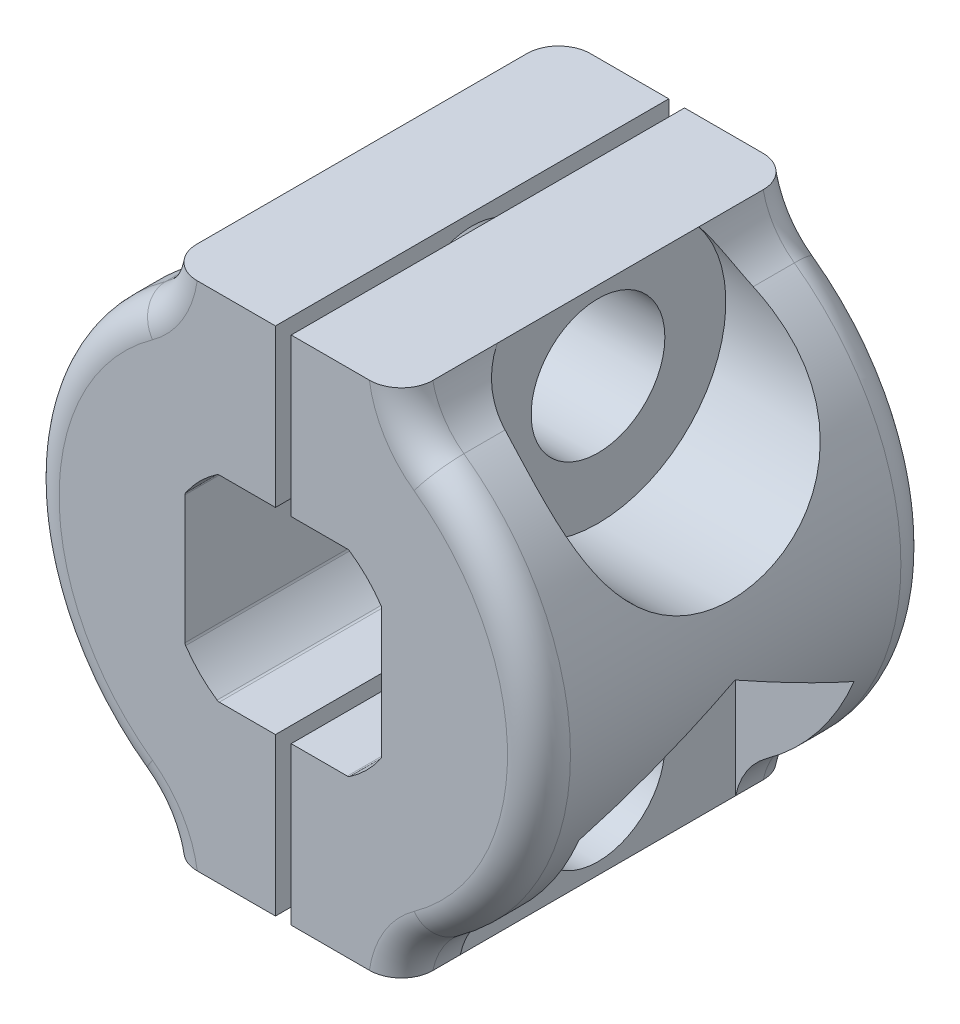
SolidWorks part; units mm, degrees
ref_plane "Front Plane" through (0, 0, 0) normal (0, 0, 1) x (1, 0, 0)
ref_plane "Top Plane" through (0, 0, 0) normal (0, 1, 0) x (1, 0, 0)
ref_plane "Right Plane" through (0, 0, 0) normal (1, 0, 0) x (0, 0, -1)
sketch "Sketch1" plane through (0, 0, 0) normal (0, 0, 1) x (1, 0, 0)
  line L6 (-3.175, 0) -> (-3.175, -2.0674)
  line L7 (-2.0674, -3.175) -> (2.0674, -3.175)
  line L8 (3.175, -2.0674) -> (3.175, 0)
  line L9 (-3.175, 2.0674) -> (-3.175, 0)
  line L10 (3.175, 0) -> (3.175, 2.0674)
  line L11 (2.0674, 3.175) -> (-2.0674, 3.175)
  arc A14 (-3.175, -2.0674) -> (-3.1531, -2.1387) centre (-3.048, -2.0674) ccw
  arc A15 (-3.1531, -2.1387) -> (-2.1387, -3.1531) centre (0, 0) ccw
  arc A16 (-2.1387, -3.1531) -> (-2.0674, -3.175) centre (-2.0674, -3.048) ccw
  arc A17 (2.0674, -3.175) -> (2.1387, -3.1531) centre (2.0674, -3.048) ccw
  arc A18 (2.1387, -3.1531) -> (3.1531, -2.1387) centre (0, 0) ccw
  arc A19 (3.1531, -2.1387) -> (3.175, -2.0674) centre (3.048, -2.0674) ccw
  arc A20 (-3, 0) -> (3, 0) centre (0, 0) ccw
  arc A21 (3, 0) -> (-3, 0) centre (0, 0) ccw
  arc A22 (3.175, 2.0674) -> (3.1531, 2.1387) centre (3.048, 2.0674) ccw
  arc A23 (3.1531, 2.1387) -> (2.1387, 3.1531) centre (0, 0) ccw
  arc A24 (2.1387, 3.1531) -> (2.0674, 3.175) centre (2.0674, 3.048) ccw
  arc A25 (-2.0674, 3.175) -> (-2.1387, 3.1531) centre (-2.0674, 3.048) ccw
  arc A26 (-2.1387, 3.1531) -> (-3.1531, 2.1387) centre (0, 0) ccw
  arc A27 (-3.1531, 2.1387) -> (-3.175, 2.0674) centre (-3.048, 2.0674) ccw
sketch "Sketch2" plane through (0, 0, 0) normal (0, 0, 1) x (1, 0, 0)
  line L0 (0, 8.255) -> (0, -8.255) construction
  line L1 (0.254, 8.2511) -> (0.254, -8.2511)
  line L2 (-0.254, 8.2511) -> (-0.254, -8.2511)
  line L3 (-0.254, 8.2511) -> (-3.81, 8.2511)
  line L4 (-3.81, 8.2511) -> (-3.81, 7.3232)
  line L5 (3.81, 8.2511) -> (3.81, 7.3232)
  line L6 (0.254, 8.2511) -> (3.81, 8.2511)
  line L7 (-3.175, 2.0674) -> (-3.175, 0)
  line L8 (-3.175, 0) -> (-3.175, -2.0674)
  line L9 (-2.0674, -3.175) -> (2.0674, -3.175)
  line L10 (3.175, -2.0674) -> (3.175, 0)
  line L11 (3.175, 0) -> (3.175, 2.0674)
  line L12 (2.0674, 3.175) -> (-2.0674, 3.175)
  line L13 (-3.175, 2.0674) -> (-3.175, 0)
  line L14 (-3.175, 0) -> (-3.175, -2.0674)
  line L15 (-2.0674, -3.175) -> (2.0674, -3.175)
  line L16 (3.175, -2.0674) -> (3.175, 0)
  line L17 (3.175, 0) -> (3.175, 2.0674)
  line L18 (2.0674, 3.175) -> (-2.0674, 3.175)
  line L19 (0, 0) -> (-8.255, 0) construction
  line L20 (-3.81, -8.2511) -> (-3.81, -7.3232)
  line L21 (-0.254, -8.2511) -> (-3.81, -8.2511)
  line L22 (3.81, -8.2511) -> (3.81, -7.3232)
  line L23 (0.254, -8.2511) -> (3.81, -8.2511)
  circle A0 centre (0, 0) radius 8.255
  arc A17 (-3.1531, 2.1387) -> (-3.175, 2.0674) centre (-3.048, 2.0674) ccw
  arc A18 (-3.175, -2.0674) -> (-3.1531, -2.1387) centre (-3.048, -2.0674) ccw
  arc A19 (-3.1531, -2.1387) -> (-2.1387, -3.1531) centre (0, 0) ccw
  arc A20 (-2.1387, -3.1531) -> (-2.0674, -3.175) centre (-2.0674, -3.048) ccw
  arc A21 (2.0674, -3.175) -> (2.1387, -3.1531) centre (2.0674, -3.048) ccw
  arc A22 (2.1387, -3.1531) -> (3.1531, -2.1387) centre (0, 0) ccw
  arc A23 (3.1531, -2.1387) -> (3.175, -2.0674) centre (3.048, -2.0674) ccw
  arc A24 (3.175, 2.0674) -> (3.1531, 2.1387) centre (3.048, 2.0674) ccw
  arc A25 (3.1531, 2.1387) -> (2.1387, 3.1531) centre (0, 0) ccw
  arc A26 (2.1387, 3.1531) -> (2.0674, 3.175) centre (2.0674, 3.048) ccw
  arc A27 (-2.0674, 3.175) -> (-2.1387, 3.1531) centre (-2.0674, 3.048) ccw
  arc A28 (-2.1387, 3.1531) -> (-3.1531, 2.1387) centre (0, 0) ccw
  arc A29 (-3.1531, 2.1387) -> (-3.175, 2.0674) centre (-3.048, 2.0674) ccw
  arc A30 (-3.175, -2.0674) -> (-3.1531, -2.1387) centre (-3.048, -2.0674) ccw
  arc A31 (-3.1531, -2.1387) -> (-2.1387, -3.1531) centre (0, 0) ccw
  arc A32 (-2.1387, -3.1531) -> (-2.0674, -3.175) centre (-2.0674, -3.048) ccw
  arc A33 (2.0674, -3.175) -> (2.1387, -3.1531) centre (2.0674, -3.048) ccw
  arc A34 (2.1387, -3.1531) -> (3.1531, -2.1387) centre (0, 0) ccw
  arc A35 (3.1531, -2.1387) -> (3.175, -2.0674) centre (3.048, -2.0674) ccw
  arc A36 (3.175, 2.0674) -> (3.1531, 2.1387) centre (3.048, 2.0674) ccw
  arc A37 (3.1531, 2.1387) -> (2.1387, 3.1531) centre (0, 0) ccw
  arc A38 (2.1387, 3.1531) -> (2.0674, 3.175) centre (2.0674, 3.048) ccw
  arc A39 (-2.0674, 3.175) -> (-2.1387, 3.1531) centre (-2.0674, 3.048) ccw
  arc A40 (-2.1387, 3.1531) -> (-3.1531, 2.1387) centre (0, 0) ccw
  dimension "D1" = 16.51
  dimension "D2" = 0.254
  dimension "D4" = 3.81
  dimension "D3" = 0
extrude "Boss-Extrude1" add sketch "Sketch2" along normal mid plane 12.7 contours A40 A39 L18 L2 A0 L15 A32 A31 A30 L14 L13 A29 | A38 A37 A36 L17 L16 A35 A34 A33 L15 L1 A0 L18 | A0 L5 L6 | A0 L3 L4 | A0 L20 L21 | A0 L23 L22 region at (4.0509, 0, 0) region at (2.8796, 7.975, 0) region at (-2.8796, 7.975, 0) region at (-4.0509, 0, 0) region at (2.8796, -7.975, 0) region at (-2.8796, -7.975, 0)
sketch "Sketch3" plane through (-0.254, 0, 0) normal (1, 0, 0) x (0, 0, -1)
  line L0 (0, 0) -> (0, 8.2511) construction
  line L2 (0, 0) -> (6.35, 0) construction
  line L3 (6.35, 2.0674) -> (6.35, -2.0674) construction
  line L4 (0, 8.2511) -> (0, 3.175)
  line L5 (-6.35, 3.175) -> (6.35, 3.175) construction
  line L6 (-6.35, 8.2511) -> (6.35, 8.2511) construction
  circle A0 centre (0, 5.713) radius 2.159
  circle A1 centre (0, -5.713) radius 2.159
  dimension "D1" = 4.318
extrude "Cut-Extrude1" cut sketch "Sketch3" against normal through all both and the other way through all contours L4 A0 | A1 | L4 A0 region at (-0.254, 5.713, -0.9163) region at (-0.254, 5.713, 0.9163) region at (-0.254, -5.713, 0)
sketch "Sketch4" plane through (0, 0, 0) normal (1, 0, 0) x (0, 0, -1)
  line L0 (0, 10.8457) -> (0, 0.5804) construction
  line L1 (-4.445, 3.1467) -> (0, 0.5804)
  line L2 (0, 0.5804) -> (4.445, 3.1467)
  line L3 (4.445, 3.1467) -> (4.445, 8.2794)
  line L4 (4.445, 8.2794) -> (0, 10.8457)
  line L5 (0, 10.8457) -> (-4.445, 8.2794)
  line L6 (-4.445, 8.2794) -> (-4.445, 3.1467)
  line L7 (-6.35, 7.3232) -> (-6.35, -7.3232) construction
  line L8 (0, 0) -> (-6.35, 0) construction
  line L9 (4.445, -8.2794) -> (0, -10.8457)
  line L10 (4.445, -3.1467) -> (4.445, -8.2794)
  line L11 (0, -0.5804) -> (4.445, -3.1467)
  line L12 (-4.445, -3.1467) -> (0, -0.5804)
  line L13 (-4.445, -8.2794) -> (-4.445, -3.1467)
  line L14 (0, -10.8457) -> (-4.445, -8.2794)
  circle A0 centre (0, 5.713) radius 4.445 construction
  circle A1 centre (0, 5.713) radius 2.159 construction
  circle A2 centre (0, 5.713) radius 2.159
  circle A3 centre (0, -5.713) radius 2.159
  dimension "D1" = 8.89
extrude "Cut-Extrude2" cut sketch "Sketch4" against normal blind 12.7 from offset 3.81 contours L5 L6 L1 L2 L3 L4 A2 region at (0, 5.713, 4.3092) offset against normal yes
extrude "Cut-Extrude3" cut sketch "Sketch4<4>" along normal blind 12.7 from offset 3.81 contours L14 L9 L10 L11 L12 L13 A3 region at (0, -9.4449, -2.1546)
sketch "Sketch4<4>" plane through (0, 0, 0) normal (1, 0, 0) x (0, 0, -1) same geometry as "Sketch4"
sketch "Sketch6" plane through (3.81, 0, 0) normal (1, 0, 0) x (0, 0, -1)
  circle A0 centre (0, 5.713) radius 4.1275
  dimension "D1" = 8.255
extrude "Cut-Extrude4" cut sketch "Sketch6" along normal blind 12.7
sketch "Sketch7" plane through (-3.81, 0, 0) normal (-1, 0, 0) x (0, 0, 1)
  circle A0 centre (0, -5.713) radius 4.1275
  dimension "D1" = 8.255
extrude "Cut-Extrude5" cut sketch "Sketch7" along normal blind 12.7
fillet "Fillet1" radius 2.54 4 edges at (-3.81, 7.3232, -5.3975) (-3.81, 7.3232, 5.3975) (-3.81, -7.3232, 5.0752) (-3.81, -7.3232, -5.0752)
fillet "Fillet2" radius 2.54 4 edges at (3.81, -7.3232, 5.3975) (3.81, -7.3232, -5.3975) (3.81, 7.3232, 5.0752) (3.81, 7.3232, -5.0752)
fillet "Fillet3" radius 1.016 6 edges at (4.1674, -7.3837, 6.35) (4.1674, 7.3837, 6.35) (4.1674, -7.3837, -6.35) (4.1674, 7.3837, -6.35) (8.255, 0, 6.35) (8.255, 0, -6.35)
fillet "Fillet4" radius 1.016 6 edges at (-4.1674, 7.3837, 6.35) (-4.1674, -7.3837, 6.35) (-4.1674, 7.3837, -6.35) (-4.1674, -7.3837, -6.35) (-8.255, 0, 6.35) (-8.255, 0, -6.35)
sketch "Sketch5" plane through (0, 0, 0) normal (0, 1, 0) x (1, 0, 0)
  line L0 (0, 0) -> (0, -13.9555) construction
ref_plane "Plane1" through (0, 0, 0) normal (-0.7071, 0.7071, 0) x (0, 0, 1)
